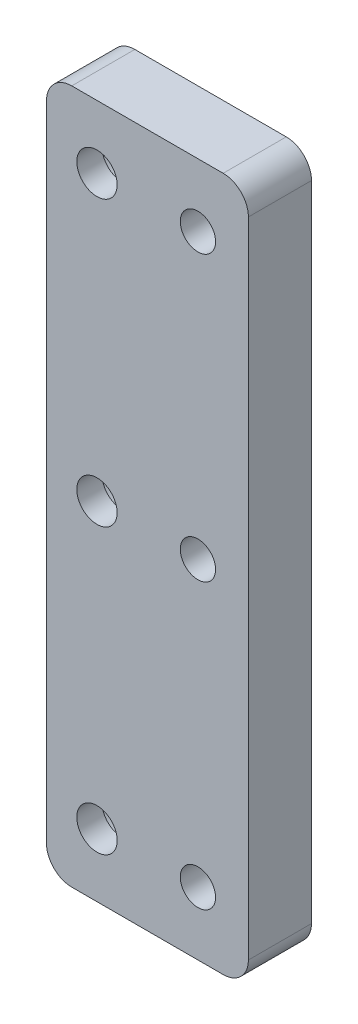
SolidWorks part; units mm, degrees
ref_plane "Front Plane" through (0, 0, 0) normal (0, 0, 1) x (1, 0, 0)
ref_plane "Top Plane" through (0, 0, 0) normal (0, 1, 0) x (1, 0, 0)
ref_plane "Right Plane" through (0, 0, 0) normal (1, 0, 0) x (0, 0, -1)
sketch "Sketch1" plane through (0, 0, 0) normal (0, 0, 1) x (1, 0, 0)
  line L1 (-4, -27.5) -> (4, -27.5)
  line L2 (-4, -27.5) -> (-4, 27.5)
  line L3 (-4, 27.5) -> (4, 27.5)
  line L4 (4, -27.5) -> (4, 27.5)
  line L5 (-4, -27.5) -> (4, 27.5) construction
  line L6 (-4, 27.5) -> (4, -27.5) construction
  point P0 (0, 0)
  dimension "D1" = 8
  dimension "D2" = 55
extrude "Boss-Extrude1" add sketch "Sketch1" along normal blind 2.5 and the other way blind 2.5
sketch "Sketch2" plane through (0, 0, 2.5) normal (0, 0, 1) x (1, 0, 0)
  line L0 (0, 22.5) -> (0, -22.5) construction
  line L1 (0, -22.5) -> (0, -27.5) construction
  line L2 (-4, -27.5) -> (4, -27.5) construction
  line L3 (0, 22.5) -> (0, 27.5) construction
  line L4 (4, 27.5) -> (-4, 27.5) construction
  circle A0 centre (0, 22.5) radius 1.6
  circle A1 centre (0, -22.5) radius 1.6
  circle A2 centre (0, 0) radius 1.6
  dimension "D2" = 3.2
  dimension "D1" = 45
extrude "Cut-Extrude1" cut sketch "Sketch2" against normal through all
sketch "Sketch3" plane through (0, 0, 2.5) normal (0, 0, 1) x (1, 0, 0)
  line L0 (-4, -27.5) -> (4, -27.5) construction
  line L1 (4, 27.5) -> (12, 27.5)
  line L2 (4, 27.5) -> (4, -27.5)
  line L3 (4, -27.5) -> (12, -27.5)
  line L4 (12, 27.5) -> (12, -27.5)
  line L5 (0, 22.5) -> (8, 22.5) construction
  line L6 (8, 22.5) -> (8, 27.5) construction
  line L7 (8, 22.5) -> (8, -27.5) construction
  line L8 (0, 0) -> (8, 0) construction
  line L9 (0, -22.5) -> (8, -22.5) construction
  circle A0 centre (0, 22.5) radius 3.25 construction
  circle A1 centre (8, 22.5) radius 1.4
  circle A2 centre (8, 0) radius 1.4
  circle A3 centre (8, -22.5) radius 1.4
  dimension "D2" = 6.5
  dimension "D3" = 2.8
  dimension "D1" = 8
extrude "Boss-Extrude3" add sketch "Sketch3" against normal through all
hole_wizard "CBORE for M5 Hex Head Bolt3" positions "3DSketch4" profile "Sketch8" counterbore size "M5" standard "ANSI Metric" end condition through all
sketch3d "3DSketch4"
  line L0 (0, 22.5, -2.5) -> (0, 22.5, 2.5) construction
  line L1 (0, -22.5, -2.5) -> (0, -22.5, 2.5) construction
  line L2 (0, 0, -2.5) -> (0, 0, 2.5) construction
  point P0 (0, 22.5, -2.5)
  point P4 (0, 0, 0)
  point P7 (0, -22.5, -2.5)
  point P11 (0, 0, -2.5)
sketch "Sketch8" plane through (0, 22.5, -2.5) normal (1, 0, 0) x (0, 1, 0)
  line L0 (0, 0) -> (0, 5)
  line L1 (0, 5) -> (1.6, 5)
  line L3 (1.6, 5) -> (1.6, 3)
  line L4 (1.6, 3) -> (3.5, 3)
  line L5 (3.5, 3) -> (3.5, 0)
  line L7 (3.5, 0) -> (0, 0)
  line L11 (0, -6.35) -> (0, 107.95) construction
  dimension "Thru Hole Dia." = 3.2
  dimension "Thru Hole Depth" = 5
  dimension "C'Bore Dia." = 7
  dimension "C'Bore Depth" = 3
fillet "Fillet1" radius 2 4 edges at (-4, -27.5, 0) (12, -27.5, 0) (-4, 27.5, 0) (12, 27.5, 0)
